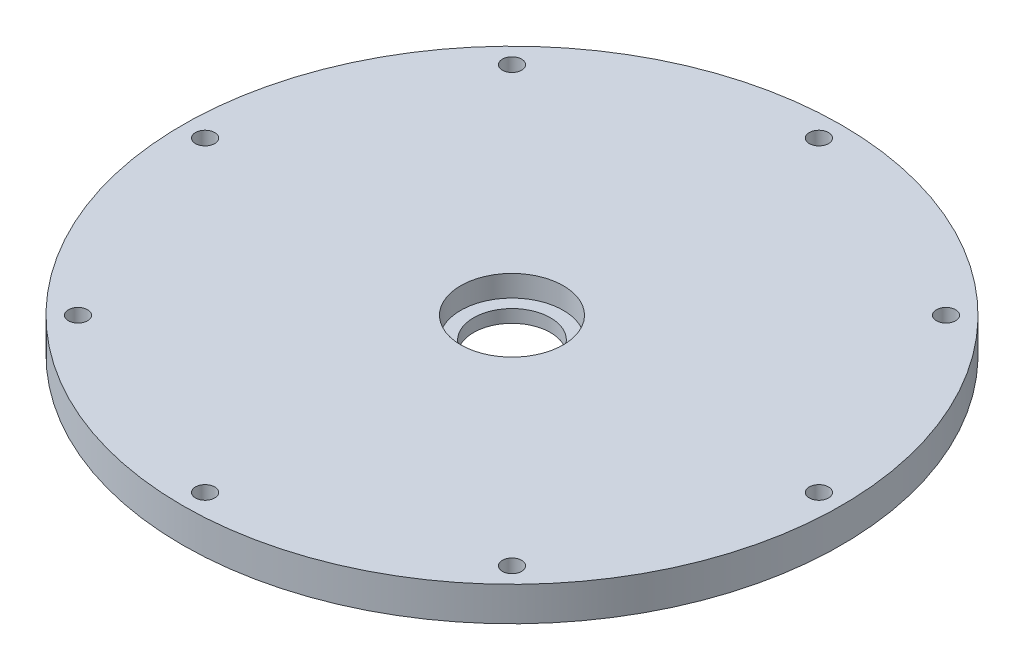
SolidWorks part; units mm, degrees
ref_plane "Front Plane" through (0, 0, 0) normal (0, 0, 1) x (1, 0, 0)
ref_plane "Top Plane" through (0, 0, 0) normal (0, 1, 0) x (1, 0, 0)
ref_plane "Right Plane" through (0, 0, 0) normal (1, 0, 0) x (0, 0, -1)
sketch "Sketch1" plane through (0, 0, 0) normal (0, 1, 0) x (1, 0, 0)
  circle A0 centre (0, 0) radius 77.1
  dimension "D1" = 154.2
extrude "Boss-Extrude1" add sketch "Sketch1" along normal blind 8
sketch "Sketch2" plane through (0, 8, 0) normal (0, 1, 0) x (1, 0, 0)
  circle A0 centre (0, 0) radius 71.8 construction
  circle A1 centre (0, 71.8) radius 2.25
  circle A2 centre (50.7703, 50.7703) radius 2.25
  circle A3 centre (71.8, 0) radius 2.25
  circle A4 centre (50.7703, -50.7703) radius 2.25
  circle A5 centre (0, -71.8) radius 2.25
  circle A6 centre (-50.7703, -50.7703) radius 2.25
  circle A7 centre (-71.8, 0) radius 2.25
  circle A8 centre (-50.7703, 50.7703) radius 2.25
  point P5 (4.0746, 96.48)
  point P6 (0, 0)
  point P14 (0, 0)
  point P22 (0, 0)
  point P23 (0, 0)
  dimension "D1" = 143.6
  dimension "D2" = 4.5
  dimension "D3" = 8
extrude "Cut-Extrude1" cut sketch "Sketch2" against normal through all
sketch "Sketch3" plane through (0, 0, 0) normal (0, -1, 0) x (1, 0, 0)
  circle A0 centre (0, 0) radius 60 construction
  circle A1 centre (60, 0) radius 3
  circle A2 centre (57.9555, -15.5291) radius 3
  circle A3 centre (51.9615, -30) radius 3
  circle A4 centre (42.4264, -42.4264) radius 3
  circle A5 centre (30, -51.9615) radius 3
  circle A6 centre (15.5291, -57.9555) radius 3
  circle A7 centre (0, -60) radius 3
  circle A8 centre (-15.5291, -57.9555) radius 3
  circle A9 centre (-30, -51.9615) radius 3
  circle A10 centre (-42.4264, -42.4264) radius 3
  circle A11 centre (-51.9615, -30) radius 3
  circle A12 centre (-57.9555, -15.5291) radius 3
  circle A13 centre (-60, 0) radius 3
  circle A14 centre (-57.9555, 15.5291) radius 3
  circle A15 centre (-51.9615, 30) radius 3
  circle A16 centre (-42.4264, 42.4264) radius 3
  circle A17 centre (-30, 51.9615) radius 3
  circle A18 centre (-15.5291, 57.9555) radius 3
  circle A19 centre (0, 60) radius 3
  circle A20 centre (15.5291, 57.9555) radius 3
  circle A21 centre (30, 51.9615) radius 3
  circle A22 centre (42.4264, 42.4264) radius 3
  circle A23 centre (51.9615, 30) radius 3
  circle A24 centre (57.9555, 15.5291) radius 3
  point P5 (-4.006, 64.2423)
  point P6 (-1.4873, 10.6594)
  point P14 (0, 0)
  dimension "D1" = 120
  dimension "D2" = 6
  dimension "D3" = 24
extrude "Cut-Extrude2" cut sketch "Sketch3" against normal blind 5
sketch "Sketch4" plane through (0, 8, 0) normal (0, 1, 0) x (1, 0, 0)
  circle A0 centre (0, 0) radius 12
  dimension "D1" = 24
extrude "Cut-Extrude3" cut sketch "Sketch4" against normal blind 5
sketch "Sketch5" plane through (0, 3, 0) normal (0, 1, 0) x (1, 0, 0)
  circle A0 centre (0, 0) radius 9
  dimension "D1" = 18
extrude "Cut-Extrude4" cut sketch "Sketch5" against normal blind 5
equation "\"N_pin\"= 24"
equation "\"R_pin\"= 60"
equation "\"d_pin\"= 13"
equation "\"e\"= 1.5"
equation "\"t_disk\"= 5"
equation "\"N_outpin\"= 8"
equation "\"R_outpin\"= 34"
equation "\"d_outpin\"= 13"
equation "\"N_lobes\"= \"N_pin\" - 1"
equation "\"d_outhole\"= \"d_outpin\" + 2 * \"e\""
equation "\"ratio\"= \"N_lobes\""
equation "\"d_center\"= 24"
equation "\"a_hole1\"= 0 / \"N_lobes\""
equation "\"a_hole2\"= 360 / \"N_disk\" / \"N_lobes\""
equation "\"a_hole3\"= 720 / \"N_disk\" / \"N_lobes\""
equation "\"N_disk\"= 3"
equation "\"t_gap\"= 0.5"
equation "\"L_stack\"= \"N_disk\" * \"t_disk\" + (\"N_disk\" - 1) * \"t_gap\""
equation "\"d_pinshaft\"= 6"
equation "\"d_ecc\"= 15"
equation "\"d_outbrg\"= 47"
equation "\"w_outbrg\"= 7"
equation "\"d_outshaft\"= 35"
equation "\"w_brg\"= 5"
equation "\"c_run\"= 0.5"
equation "\"c_ax\"= 2 * \"t_gap\""
equation "\"D_pocket\"= 2 * \"R_pin\" + \"d_pin\" + 2 * \"c_run\""
equation "\"h_pocket\"= \"L_stack\" + 2 * \"c_ax\""
equation "\"t_floor\"= 8"
equation "\"d_insert\"= 5.6"
equation "\"N_bolt\"= 8"
equation "\"R_bolt\"= \"D_pocket\" / 2 + 2 + \"d_insert\" / 2"
equation "\"D_housing\"= 2 * (\"R_bolt\" + \"d_insert\" / 2 + 2.5)"
equation "\"D1@Sketch1\"=\"D_housing\""
equation "\"D1@Boss-Extrude1\"=\"t_floor\""
equation "\"D1@Sketch2\"=\"R_bolt\"*2"
equation "\"D3@Sketch2\"=\"N_bolt\""
equation "\"D1@Sketch3\"=\"R_pin\"*2"
equation "\"D2@Sketch3\"=\"d_pinshaft\""
equation "\"D3@Sketch3\"=\"N_pin\""
equation "\"D1@Cut-Extrude2\"=\"t_floor\"-3"
equation "\"D1@Sketch4\"=\"d_center\""
equation "\"D1@Cut-Extrude3\"=\"w_brg\""
equation "\"D1@Sketch5\"=\"d_ecc\"+3"
